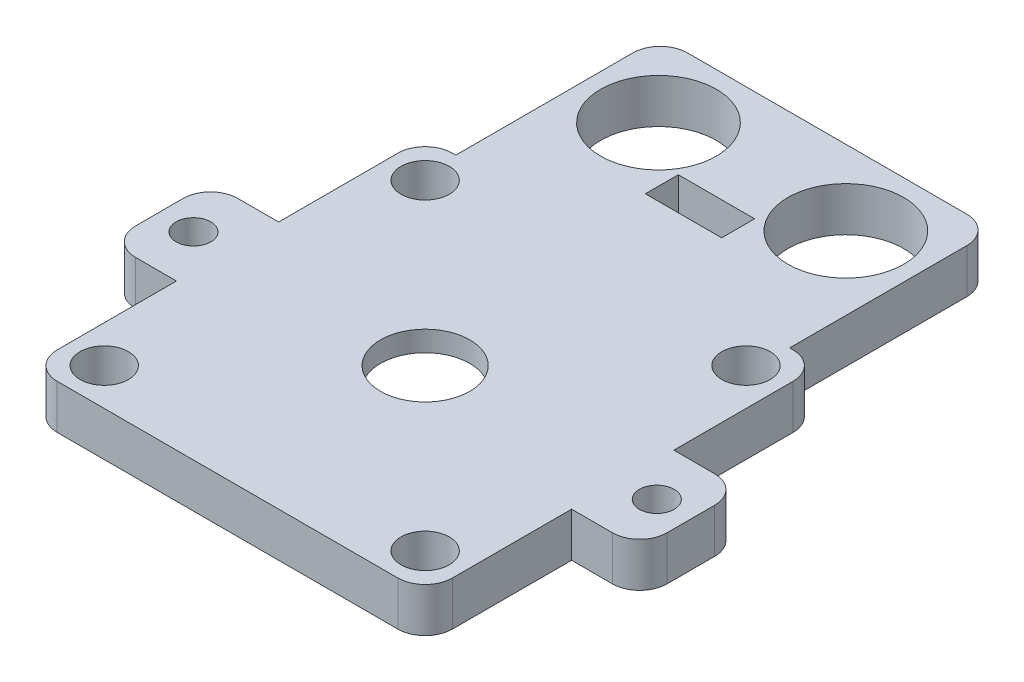
SolidWorks part; units mm, degrees
ref_plane "Front Plane" through (0, 0, 0) normal (0, 0, 1) x (1, 0, 0)
ref_plane "Top Plane" through (0, 0, 0) normal (0, 1, 0) x (1, 0, 0)
ref_plane "Right Plane" through (0, 0, 0) normal (1, 0, 0) x (0, 0, -1)
sketch "Sketch1" plane through (0, 0, 0) normal (0, 1, 0) x (1, 0, 0)
  circle A0 centre (0, 0) radius 20
  circle A1 centre (0, 0) radius 21
  dimension "D1" = 40
  dimension "D2" = 42
extrude "Boss-Extrude1" add sketch "Sketch1" along normal blind 3.5
ref_plane "Plane1" through (0, 3.5, 0) normal (0, 1, 0) x (1, 0, 0)
sketch "Sketch2" plane through (0, 3.5, 0) normal (0, 1, 0) x (1, 0, 0)
  line L0 (-23.55, 0) -> (23.55, 0) construction
  line L1 (-29, -29) -> (29, -29)
  line L2 (-29, -29) -> (-29, 29)
  line L3 (-29, 29) -> (29, 29)
  line L4 (29, -29) -> (29, 29)
  line L5 (-29, -29) -> (29, 29) construction
  line L6 (-29, 29) -> (29, -29) construction
  line L7 (-28.2, -28.2) -> (28.2, -28.2) construction
  line L8 (-28.2, -28.2) -> (-28.2, 28.2) construction
  line L9 (-28.2, 28.2) -> (28.2, 28.2) construction
  line L10 (28.2, -28.2) -> (28.2, 28.2) construction
  line L11 (-28.2, -28.2) -> (28.2, 28.2) construction
  line L12 (-28.2, 28.2) -> (28.2, -28.2) construction
  line L13 (-23.55, 28.2) -> (-23.55, 23.55) construction
  line L14 (-23.55, 23.55) -> (-28.2, 23.55) construction
  line L15 (0, 28.2) -> (0, -28.2) construction
  line L16 (0, 29) -> (0, 49) construction
  line L17 (-22.5, 49) -> (22.5, 49) construction
  line L18 (-22.5, 49) -> (-22.5, 29) construction
  line L19 (22.5, 49) -> (22.5, 29) construction
  line L20 (0, 49) -> (0, 48) construction
  line L21 (-4.9, 48) -> (4.9, 48) construction
  line L22 (-4.9, 48) -> (-4.9, 44.56) construction
  line L23 (-4.9, 44.56) -> (4.9, 44.56) construction
  line L24 (4.9, 44.56) -> (4.9, 48) construction
  line L25 (-24.5, 29) -> (-24.5, 51)
  line L26 (-24.5, 51) -> (24.5, 51)
  line L27 (24.5, 51) -> (24.5, 29)
  line L28 (-13.76, 39) -> (13.76, 39) construction
  line L29 (-5.6, 48.7) -> (5.6, 48.7)
  line L31 (5.6, 43.86) -> (-5.6, 43.86)
  line L32 (-5.6, 43.86) -> (-5.6, 48.7)
  line L33 (5.6, 43.86) -> (5.6, 48.7)
  line L34 (-24.5, 51) -> (-24.5, 59)
  line L35 (-24.5, 59) -> (24.5, 59)
  line L36 (24.5, 59) -> (24.5, 51)
  line L37 (-29, 7.5) -> (-39, 7.5)
  line L38 (-39, 7.5) -> (-39, -7.5)
  line L39 (-39, -7.5) -> (-29, -7.5)
  line L40 (39, -7.5) -> (29, -7.5)
  line L41 (39, 7.5) -> (39, -7.5)
  line L42 (29, 7.5) -> (39, 7.5)
  circle A0 centre (-23.55, 23.55) radius 2.55 construction
  circle A1 centre (23.55, 23.55) radius 2.55 construction
  circle A2 centre (23.55, -23.55) radius 2.55 construction
  circle A3 centre (-23.55, -23.55) radius 2.55 construction
  circle A4 centre (0, 0) radius 5.5563 construction
  circle A5 centre (13.76, 39) radius 7.5 construction
  circle A6 centre (-13.76, 39) radius 7.5 construction
  circle A7 centre (-13.76, 39) radius 8.5
  circle A8 centre (13.76, 39) radius 8.5
  circle A9 centre (0, 0) radius 6.55
  circle A10 centre (-23.55, 23.55) radius 3.55
  circle A11 centre (23.55, 23.55) radius 3.55
  circle A12 centre (23.55, -23.55) radius 3.55
  circle A13 centre (-23.55, -23.55) radius 3.55
  circle A14 centre (-34, 0) radius 2.55
  circle A15 centre (34, 0) radius 2.55
  point P0 (0, 0)
  point P5 (0, 0)
  point P15 (0, 0)
  point P34 (0, 49)
  point P40 (0, 48)
  point P49 (0, 39)
  point P56 (0, 43.86)
  point P59 (0, 48.7)
  point P70 (-39, 0)
  point P71 (0, 0)
  point P74 (0, 0)
  point P76 (0, 0)
  dimension "D4" = 5.1
  dimension "D5" = 11.1125
  dimension "D15" = 15
  dimension "D16" = 17
  dimension "D17" = 0.7
  dimension "D20" = 13.1
  dimension "D21" = 7.1
  dimension "D22" = 8
  dimension "D26" = 5.1
  dimension "D1" = 58
  dimension "D2" = 56.4
  dimension "D3" = 47.1
  dimension "D6" = 20
  dimension "D7" = 45
  dimension "D8" = 1
  dimension "D9" = 9.8
  dimension "D10" = 3.44
  dimension "D11" = 2
  dimension "D12" = 2
  dimension "D13" = 2
  dimension "D14" = 27.52
  dimension "D18" = 0.7
  dimension "D19" = 0.7
  dimension "D23" = 34
  dimension "D24" = 10
  dimension "D25" = 15
extrude "Boss-Extrude2" add sketch "Sketch2" along normal blind 3 contours L1 L4 L3 L2 A4 A1 A0 A2 A3 | L27 L26 L25 L3 A8 A7 L33 L31 L32 L29 | L38 L39 L2 L37 A14 | L42 L4 L40 L41 A15 region at (-28.1798, 3.5, 18.25) region at (-34, 3.5, 7.3197) region at (29.1803, 3.5, 0) region at (0, 3.5, -40.1992)
sketch "Sketch3" plane through (0, 3.5, 0) normal (0, 1, 0) x (1, 0, 0)
  line L0 (-5.6, 48.7) -> (5.6, 48.7)
  line L1 (5.6, 48.7) -> (5.6, 43.86)
  line L2 (5.6, 43.86) -> (-5.6, 43.86)
  line L3 (-5.6, 43.86) -> (-5.6, 48.7)
  line L4 (-13.76, 47.5) -> (-13.76, 30.5) construction
  line L5 (13.76, 47.5) -> (13.76, 30.5) construction
  line L6 (-24.5, 29) -> (24.5, 29)
  line L7 (24.5, 29) -> (24.5, 51)
  line L8 (24.5, 51) -> (-24.5, 51)
  line L9 (-24.5, 51) -> (-24.5, 29)
  line L10 (-24.5, 51) -> (-24.5, 59)
  line L11 (-24.5, 59) -> (24.5, 59)
  line L12 (24.5, 59) -> (24.5, 51)
  circle A0 centre (-13.76, 39) radius 8.5 construction
  circle A1 centre (-13.76, 39) radius 8.5
  circle A2 centre (13.76, 39) radius 8.5 construction
  circle A3 centre (13.76, 39) radius 8.5
  dimension "D1" = 8
sketch "Sketch4" plane through (0, 3.5, 0) normal (0, 1, 0) x (1, 0, 0)
  line L4 (-5.6791, 42.84) -> (-5.6791, 38)
  line L5 (5.5209, 38) -> (5.5209, 42.84)
  line L10 (-24.5, 29) -> (-24.5, 37)
  line L11 (-24.5, 51) -> (-24.5, 29) construction
  line L12 (24.5, 29) -> (24.5, 37)
  line L13 (24.5, 29) -> (24.5, 51) construction
  line L14 (-24.5, 37) -> (-24.5, 59)
  line L15 (24.5, 37) -> (24.5, 59)
  line L16 (-24.5, 59) -> (24.5, 59)
  line L17 (-24.5, 37) -> (24.5, 37)
  line L18 (0, 59) -> (0, 37) construction
  line L23 (-5.6791, 38) -> (5.5209, 38)
  line L24 (5.5209, 42.84) -> (-5.6791, 42.84)
  line L25 (-5.6791, 58) -> (5.5209, 58) construction
  line L26 (5.5209, 58) -> (5.5209, 53.16) construction
  line L27 (5.5209, 53.16) -> (-5.6791, 53.16) construction
  line L28 (-5.6791, 53.16) -> (-5.6791, 58) construction
  line L29 (-13.75, 56.5) -> (-13.75, 39.5) construction
  line L30 (-13.75, 48) -> (13.75, 48) construction
  circle A4 centre (-13.75, 48) radius 8.5
  circle A5 centre (13.75, 48) radius 8.5
  point P53 (0, 48)
  dimension "D2" = 17
  dimension "D1" = 8
  dimension "D3" = 22
  dimension "D4" = 1
  dimension "D5" = 5.5209
  dimension "D6" = 11.2
  dimension "D7" = 4.84
  dimension "D8" = 27.5
extrude "Boss-Extrude3" add sketch "Sketch2<4>" against normal up to surface (3.5 mm away) contours L27 L26 L25 L3 A8 A7 L33 L31 L32 L29 | L1 L4 L3 L2 A13 A12 A11 A10 A9 | L38 L39 L2 L37 A14 | L42 L4 L40 L41 A15 region at (-28.1798, 3.5, 18.25) region at (-34, 3.5, 7.3197) region at (29.1803, 3.5, 0) region at (0, 3.5, -40.1992) up to face at (0, 0, 21)
sketch "Sketch2<4>" plane through (0, 3.5, 0) normal (0, 1, 0) x (1, 0, 0) same geometry as "Sketch2"
extrude "Cut-Extrude3" cut sketch "Sketch1<3>" along normal offset from surface (3.5 mm away) 3 contours A0 region at (0, 0, 0) up to face at (-23.55, 6.5, 27.1)
sketch "Sketch1<3>" plane through (0, 0, 0) normal (0, 1, 0) x (1, 0, 0) same geometry as "Sketch1"
extrude "Ignore" add sketch "Sketch3" along normal up to surface and the other way up to surface contours L3 L2 L1 L0 | L12 L11 L10 L8 | A3 | A1 region at (0, 3.5, -46.28) region at (0, 3.5, -55) region at (-13.76, 3.5, -39) region at (13.76, 3.5, -39) up to face at (-23.55, 6.5, 27.1) other way up to face at (0, 0, 20)
extrude "Cut-Extrude2" cut sketch "Sketch4" along normal up to surface and the other way up to surface contours A4 | A5 | L28 L27 L26 L25 | L5 L24 L4 L23 region at (-0.0791, 3.5, -40.42) region at (-13.75, 3.5, -48) region at (13.75, 3.5, -48) up to face at (-23.55, 6.5, 27.1) other way up to face at (0, 0, 20)
fillet "Fillet1" radius 4 10 edges at (29, 3.25, -29) (-29, 3.25, -29) (24.5, 3.25, -59) (-24.5, 3.25, -59) (39, 3.25, -7.5) (39, 3.25, 7.5) (29, 3.25, 29) (-29, 3.25, 29) (-39, 3.25, -7.5) (-39, 3.25, 7.5)
